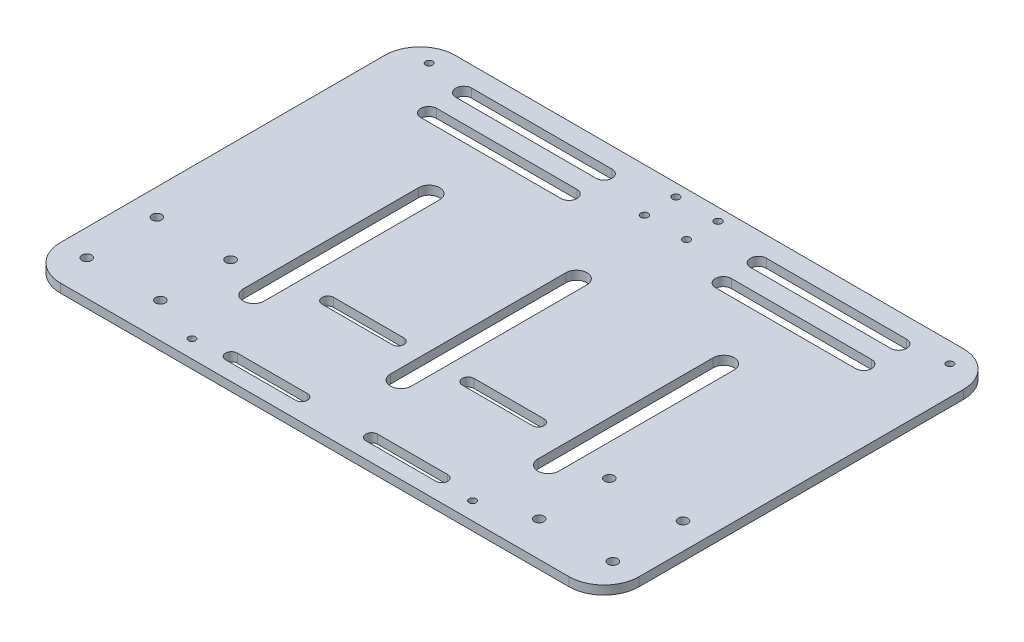
SolidWorks part; units mm, degrees
ref_plane "前视基准面" through (0, 0, 0) normal (0, 0, 1) x (1, 0, 0)
ref_plane "上视基准面" through (0, 0, 0) normal (0, 1, 0) x (1, 0, 0)
ref_plane "右视基准面" through (0, 0, 0) normal (1, 0, 0) x (0, 0, -1)
sketch "草图1" plane through (0, 0, 0) normal (0, 1, 0) x (1, 0, 0)
  line L1 (-15.2985, 237.1784) -> (314.7015, 237.1784)
  line L2 (-15.2985, 237.1784) -> (-15.2985, 12.1784)
  line L3 (-15.2985, 12.1784) -> (314.7015, 12.1784)
  line L4 (314.7015, 237.1784) -> (314.7015, 12.1784)
  dimension "D1" = 330
  dimension "D2" = 225
extrude "凸台-拉伸1" add sketch "草图1" along normal blind 5
sketch "草图2" plane through (0, 5, 0) normal (0, 1, 0) x (1, 0, 0)
  line L0 (149.7015, 237.1784) -> (149.7015, 12.1784) construction
  line L1 (314.7015, 237.1784) -> (-15.2985, 237.1784) construction
  line L2 (-15.2985, 12.1784) -> (314.7015, 12.1784) construction
  line L3 (137.7015, 230.1784) -> (137.7015, 206.5288) construction
  line L4 (137.7015, 230.1784) -> (161.7015, 212.1784) construction
  line L5 (161.7015, 230.1784) -> (137.7015, 212.1784) construction
  line L6 (149.7015, 221.1784) -> (50149.7015, 221.1784) construction
  line L7 (25.7015, 221.1784) -> (105.7015, 221.1784) construction
  line L8 (25.7015, 225.7154) -> (105.7015, 225.7154)
  line L9 (25.7015, 216.6414) -> (105.7015, 216.6414)
  line L10 (273.7015, 221.1784) -> (193.7015, 221.1784) construction
  line L11 (273.7015, 225.7154) -> (193.7015, 225.7154)
  line L12 (273.7015, 216.6414) -> (193.7015, 216.6414)
  line L13 (25.7015, 201.1784) -> (105.7015, 201.1784) construction
  line L14 (25.7015, 205.7154) -> (105.7015, 205.7154)
  line L15 (25.7015, 196.6414) -> (105.7015, 196.6414)
  line L16 (273.7015, 201.1784) -> (193.7015, 201.1784) construction
  line L17 (273.7015, 205.7154) -> (193.7015, 205.7154)
  line L18 (273.7015, 196.6414) -> (193.7015, 196.6414)
  circle A0 centre (137.7015, 230.1784) radius 2.1
  circle A1 centre (161.7015, 230.1784) radius 2.1
  circle A2 centre (137.7015, 212.1784) radius 2.1
  circle A3 centre (161.7015, 212.1784) radius 2.1
  arc A4 (25.7015, 225.7154) -> (25.7015, 216.6414) centre (25.7015, 221.1784) ccw
  arc A5 (105.7015, 216.6414) -> (105.7015, 225.7154) centre (105.7015, 221.1784) ccw
  arc A6 (273.7015, 225.7154) -> (273.7015, 216.6414) centre (273.7015, 221.1784) cw
  arc A7 (193.7015, 216.6414) -> (193.7015, 225.7154) centre (193.7015, 221.1784) cw
  arc A8 (25.7015, 205.7154) -> (25.7015, 196.6414) centre (25.7015, 201.1784) ccw
  arc A9 (105.7015, 196.6414) -> (105.7015, 205.7154) centre (105.7015, 201.1784) ccw
  arc A10 (273.7015, 205.7154) -> (273.7015, 196.6414) centre (273.7015, 201.1784) cw
  arc A11 (193.7015, 196.6414) -> (193.7015, 205.7154) centre (193.7015, 201.1784) cw
  point P14 (149.7015, 221.1784)
  point P20 (65.7015, 221.1784)
  point P27 (233.7015, 221.1784)
  point P34 (65.7015, 201.1784)
  point P41 (233.7015, 201.1784)
  dimension "D1" = 4.2
  dimension "D9" = 4.2
  dimension "D10" = 4.2
  dimension "D2" = 24
  dimension "D3" = 18
  dimension "D4" = 18
  dimension "D5" = 24
  dimension "D6" = 7
  dimension "D7" = 80
  dimension "D8" = 84
  dimension "D11" = 84
  dimension "D12" = 20
  dimension "D13" = 80
extrude "切除-拉伸1" cut sketch "草图2" against normal through all
sketch "草图3" plane through (0, 5, 0) normal (0, 1, 0) x (1, 0, 0)
  line L0 (-15.4564, 52.1784) -> (314.5436, 52.1784) construction
  line L1 (-15.2985, 237.1784) -> (-15.2985, 12.1784) construction
  line L2 (-15.2985, 12.1784) -> (314.7015, 12.1784) construction
  line L3 (314.7015, 12.1784) -> (314.7015, 237.1784) construction
  line L4 (149.7015, 462.1784) -> (149.7015, 12.1784) construction
  line L5 (89.7015, 79.6784) -> (129.7015, 79.6784) construction
  line L6 (89.7015, 83.0076) -> (129.7015, 83.0076)
  line L7 (89.7015, 76.3492) -> (129.7015, 76.3492)
  line L8 (209.7015, 79.6784) -> (169.7015, 79.6784) construction
  line L9 (209.7015, 83.0076) -> (169.7015, 83.0076)
  line L10 (209.7015, 76.3492) -> (169.7015, 76.3492)
  line L11 (89.7015, 24.6784) -> (129.7015, 24.6784) construction
  line L12 (89.7015, 21.3492) -> (129.7015, 21.3492)
  line L13 (89.7015, 28.0076) -> (129.7015, 28.0076)
  line L14 (209.7015, 24.6784) -> (169.7015, 24.6784) construction
  line L15 (209.7015, 21.3492) -> (169.7015, 21.3492)
  line L16 (209.7015, 28.0076) -> (169.7015, 28.0076)
  circle A0 centre (-0.2985, 32.1784) radius 2.75
  circle A1 centre (-0.2985, 72.1784) radius 2.75
  circle A2 centre (41.7015, 32.1784) radius 2.75
  circle A3 centre (41.7015, 72.1784) radius 2.75
  circle A4 centre (257.7015, 72.1784) radius 2.75
  circle A5 centre (257.7015, 32.1784) radius 2.75
  circle A6 centre (299.7015, 72.1784) radius 2.75
  circle A7 centre (299.7015, 32.1784) radius 2.75
  arc A8 (89.7015, 83.0076) -> (89.7015, 76.3492) centre (89.7015, 79.6784) ccw
  arc A9 (129.7015, 76.3492) -> (129.7015, 83.0076) centre (129.7015, 79.6784) ccw
  arc A10 (209.7015, 83.0076) -> (209.7015, 76.3492) centre (209.7015, 79.6784) cw
  arc A11 (169.7015, 76.3492) -> (169.7015, 83.0076) centre (169.7015, 79.6784) cw
  arc A12 (89.7015, 21.3492) -> (89.7015, 28.0076) centre (89.7015, 24.6784) cw
  arc A13 (129.7015, 28.0076) -> (129.7015, 21.3492) centre (129.7015, 24.6784) cw
  arc A14 (209.7015, 21.3492) -> (209.7015, 28.0076) centre (209.7015, 24.6784) ccw
  arc A15 (169.7015, 28.0076) -> (169.7015, 21.3492) centre (169.7015, 24.6784) ccw
  point P15 (149.7015, 237.1784)
  point P29 (109.7015, 79.6784)
  point P36 (189.7015, 79.6784)
  point P43 (109.7015, 24.6784)
  point P50 (189.7015, 24.6784)
  dimension "D5" = 5.5
  dimension "D6" = 5.5
  dimension "D7" = 40
  dimension "D9" = 40
  dimension "D1" = 40
  dimension "D2" = 42
  dimension "D3" = 20
  dimension "D4" = 15
  dimension "D8" = 27.5
extrude "切除-拉伸2" cut sketch "草图3" against normal through all
sketch "草图5" plane through (0, 5, 0) normal (0, 1, 0) x (1, 0, 0)
  line L0 (149.7015, 237.1784) -> (149.7015, -49762.8216) construction
  line L1 (314.7015, 237.1784) -> (-15.2985, 237.1784) construction
  line L2 (-28.7911, 85.1784) -> (354.7976, 85.1784) construction
  line L3 (149.7015, 161.4116) -> (149.7015, 61.4116) construction
  line L4 (155.7015, 161.4116) -> (155.7015, 61.4116)
  line L5 (143.7015, 161.4116) -> (143.7015, 61.4116)
  line L6 (233.7015, 161.4116) -> (233.7015, 61.4116) construction
  line L7 (239.7015, 161.4116) -> (239.7015, 61.4116)
  line L8 (227.7015, 161.4116) -> (227.7015, 61.4116)
  line L9 (65.7015, 161.4116) -> (65.7015, 61.4116) construction
  line L10 (59.7015, 161.4116) -> (59.7015, 61.4116)
  line L11 (71.7015, 161.4116) -> (71.7015, 61.4116)
  arc A0 (155.7015, 161.4116) -> (143.7015, 161.4116) centre (149.7015, 161.4116) ccw
  arc A1 (143.7015, 61.4116) -> (155.7015, 61.4116) centre (149.7015, 61.4116) ccw
  arc A2 (239.7015, 161.4116) -> (227.7015, 161.4116) centre (233.7015, 161.4116) ccw
  arc A3 (227.7015, 61.4116) -> (239.7015, 61.4116) centre (233.7015, 61.4116) ccw
  arc A4 (59.7015, 161.4116) -> (71.7015, 161.4116) centre (65.7015, 161.4116) cw
  arc A5 (71.7015, 61.4116) -> (59.7015, 61.4116) centre (65.7015, 61.4116) cw
  point P4 (149.7015, 237.1784)
  point P9 (149.7015, 111.4116)
  point P17 (233.7015, 111.4116)
  point P23 (65.7015, 111.4116)
  dimension "D3" = 6
  dimension "D1" = 152
  dimension "D2" = 100
  dimension "D5" = 84
  dimension "D4" = 2
extrude "切除-拉伸4" cut sketch "草图5" against normal through all
sketch "草图6" plane through (0, 5, 0) normal (0, 1, 0) x (1, 0, 0)
  line L0 (314.7015, 12.1784) -> (-15.2985, 237.1784) construction
  line L1 (314.7015, 237.1784) -> (-15.2985, 12.1784) construction
  line L2 (149.7015, 237.1784) -> (149.7015, 50237.1784) construction
  line L3 (314.7015, 237.1784) -> (-15.2985, 237.1784) construction
  line L4 (149.7015, 22.1784) -> (-49850.2985, 22.1784) construction
  line L5 (-15.2985, 12.1784) -> (314.7015, 12.1784) construction
  circle A0 centre (1.226, 225.9117) radius 2
  circle A1 centre (298.1769, 225.9117) radius 2
  circle A2 centre (69.7015, 22.1784) radius 2
  circle A3 centre (229.7015, 22.1784) radius 2
  point P14 (149.7015, 237.1784)
  dimension "D1" = 4
  dimension "D4" = 4
  dimension "D2" = 20
  dimension "D3" = 10
  dimension "D5" = 80
extrude "切除-拉伸5" cut sketch "草图6" against normal through all
fillet "圆角1" radius 20 4 edges at (314.7015, 2.5, -12.1784) (314.7015, 2.5, -237.1784) (-15.2985, 2.5, -237.1784) (-15.2985, 2.5, -12.1784)
